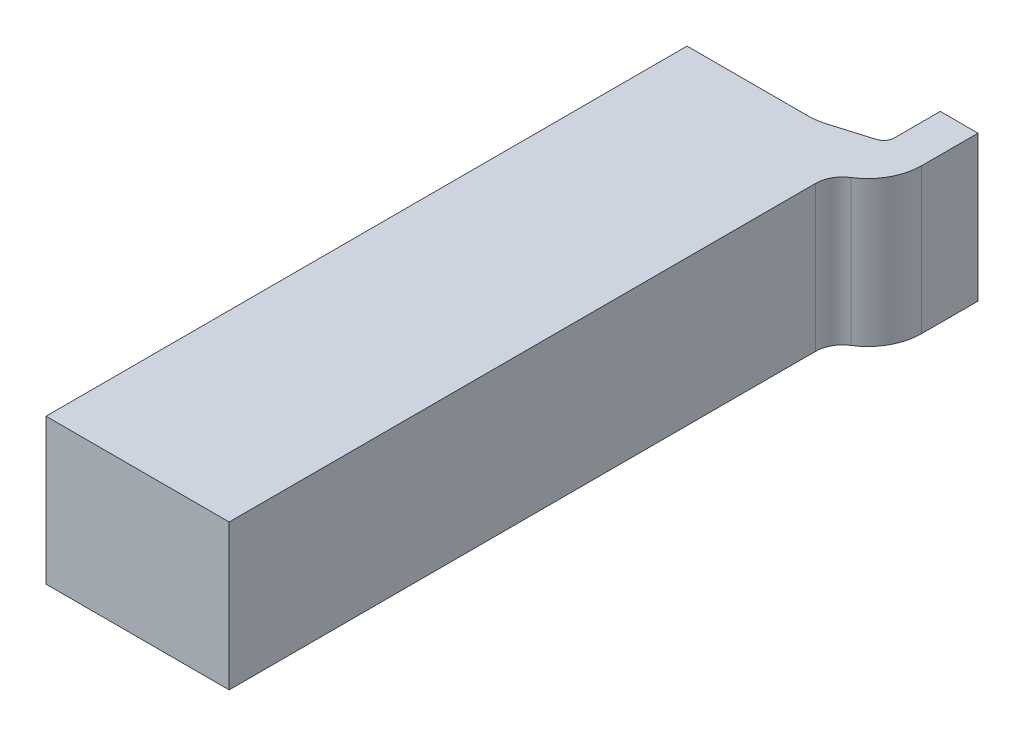
SolidWorks part; units mm, degrees
ref_plane "Спереди" through (0, 0, 0) normal (0, 0, 1) x (1, 0, 0)
ref_plane "Сверху" through (0, 0, 0) normal (0, 1, 0) x (1, 0, 0)
ref_plane "Справа" through (0, 0, 0) normal (1, 0, 0) x (0, 0, -1)
sketch "Эскиз1" plane through (0, 0, 0) normal (0, 1, 0) x (1, 0, 0)
  line L0 (0, 59.5) -> (0, -59.5) construction
  line L1 (-17, 59.5) -> (17, 59.5)
  line L2 (-17, 59.5) -> (-17, -59.5)
  line L3 (-17, -59.5) -> (17, -59.5)
  line L4 (17, 59.5) -> (17, -59.5)
  line L6 (-17, 0) -> (17, 0) construction
  point P6 (0, 0)
  dimension "D1" = 34
  dimension "D2" = 119
extrude "тело" add sketch "Эскиз1" along normal blind 13.5 and the other way blind 13.5
sketch "Эскиз2" plane through (17, 0, 0) normal (1, 0, 0) x (0, 0, -1)
  line L0 (-59.5, 13.5) -> (59.5, 13.5) construction
  line L1 (52.5, 13.5) -> (72.5, 13.5)
  line L2 (52.5, 13.5) -> (52.5, -13.5)
  line L3 (52.5, -13.5) -> (72.5, -13.5)
  line L4 (72.5, 13.5) -> (72.5, -13.5)
  line L5 (-59.5, -13.5) -> (59.5, -13.5) construction
  line L6 (59.5, -13.5) -> (59.5, 13.5) construction
  dimension "D1" = 7
  dimension "D2" = 13
extrude "выступ проводов" add sketch "Эскиз2" along normal blind 7
chamfer "Фаска1" distance 10 distance2 3 1 edges at (17, 0, -59.5) first distance on face at (0, 0, -59.5)
fillet "Скругление2" radius 10 2 edges at (7, 0, -59.5) (24, 0, -52.5)
fillet "Скругление3" radius 5 1 edges at (17, 0, -52.5)
fillet "Скругление4" radius 2 1 edges at (17, 0, -62.5)
